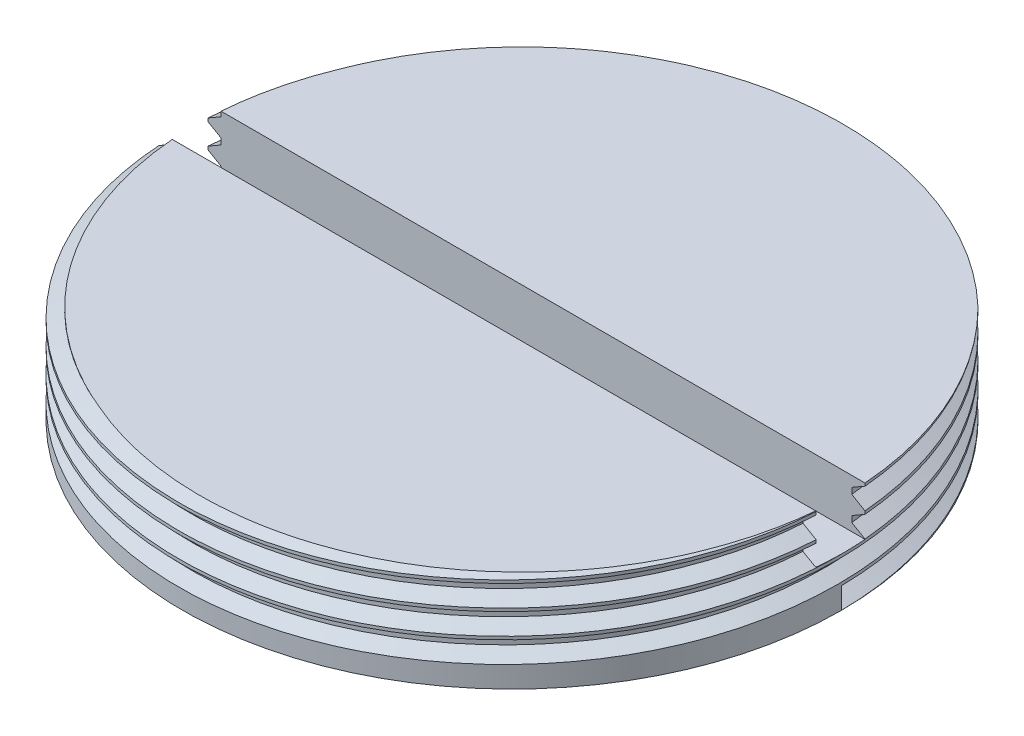
SolidWorks part; units mm, degrees
material "1060 Сплав"
ref_plane "Спереди" through (0, 0, 0) normal (0, 0, 1) x (1, 0, 0)
ref_plane "Сверху" through (0, 0, 0) normal (0, 1, 0) x (1, 0, 0)
ref_plane "Справа" through (0, 0, 0) normal (1, 0, 0) x (0, 0, -1)
sketch "Эскиз1" plane through (0, 0, 0) normal (0, 1, 0) x (1, 0, 0)
  circle A0 centre (0, 0) radius 13.5
  dimension "D1" = 27
extrude "Бобышка-Вытянуть1" add sketch "Эскиз1" along normal blind 4
sketch "Эскиз2" plane through (0, 4, 0) normal (0, 1, 0) x (1, 0, 0)
  line L1 (-16, 1) -> (16, 1)
  line L2 (-16, 1) -> (-16, -1)
  line L3 (-16, -1) -> (16, -1)
  line L4 (16, 1) -> (16, -1)
  line L5 (-16, 1) -> (16, -1) construction
  line L6 (-16, -1) -> (16, 1) construction
  point P1 (0, 0)
  dimension "D1" = 2
  dimension "D2" = 32
extrude "Вырез-Вытянуть1" cut sketch "Эскиз2" against normal blind 2
thread "Резьба1" pitch 1 method cut profile "Профиль резьбы1" start angle 0, offset 0, length 4, pitch 1, diameter 27
ref_plane "Плоскость1" through (13.5, 0, 0) normal (0, 0, 1) x (1, 0, 0)
sketch "Профиль резьбы1" plane through (13.5, 0, 0) normal (0, 0, 1) x (1, 0, 0)
  line L0 (0, 0) -> (0, 1) construction
  line L11 (0, 0) -> (0, 0.875)
  line L12 (0, 0.875) -> (-0.5413, 0.5625)
  line L13 (-0.5413, 0.5625) -> (-0.5413, 0.3125)
  line L15 (-0.5413, 0.3125) -> (0, 0)
  line L17 (-0.5413, 0.4375) -> (0, 0.4375) construction
  point P2 (0, 0)
  dimension "Pitch" = 1
  dimension "Profile_Angle" = 60
  dimension "Profile_Land" = 0.25
  dimension "Profile_Height" = 0.5413
